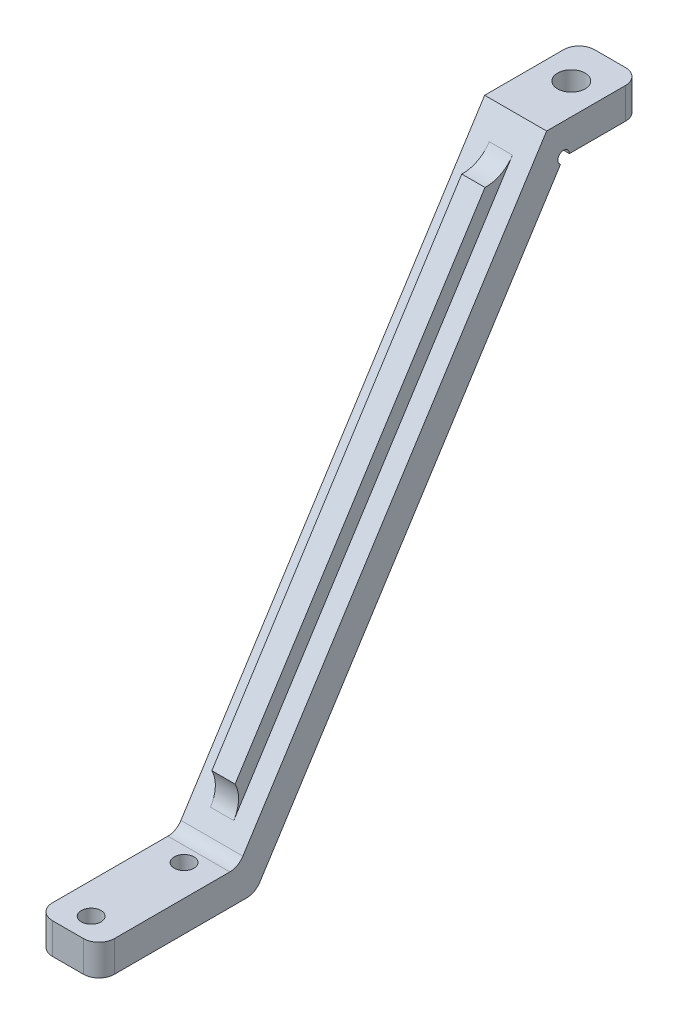
SolidWorks part; units mm, degrees
material "ABS"
ref_plane "前视基准面" through (0, 0, 0) normal (0, 0, 1) x (1, 0, 0)
ref_plane "上视基准面" through (0, 0, 0) normal (0, 1, 0) x (1, 0, 0)
ref_plane "右视基准面" through (0, 0, 0) normal (1, 0, 0) x (0, 0, -1)
other "Configuration Table"
sketch "草图1" plane through (0, 0, 0) normal (1, 0, 0) x (0, 0, -1)
  line L0 (-18, 0) -> (0, 0)
  line L1 (0, 0) -> (39.8071, 62.4)
  line L2 (39.8071, 62.4) -> (52, 62.4)
  line L3 (52, 62.4) -> (52, 58.4)
  line L4 (52, 58.4) -> (42, 58.4)
  line L5 (42, 58.4) -> (2.1929, -4)
  line L6 (2.1929, -4) -> (-18, -4)
  line L7 (-18, -4) -> (-18, 0)
  point P3 (82.8922, 68.3831)
  point P10 (42, 58.4)
  point P12 (51.9561, 62.4)
  dimension "D1" = 4
  dimension "D2" = 4
  dimension "D3" = 4
  dimension "D4" = 18
  dimension "D5" = 10
extrude "凸台-拉伸1" add sketch "草图1" along normal mid plane 8
sketch "草图2" plane through (0, 0, 0) normal (0, 1, 0) x (1, 0, 0)
  line L0 (0, -15) -> (0, -3) construction
  line L1 (0, -9) -> (4, -9) construction
  line L2 (4, 0) -> (4, -18) construction
  circle A0 centre (0, -3) radius 1.275
  circle A1 centre (0, -15) radius 1.275
  dimension "D1" = 2.55
  dimension "D2" = 12
extrude "切除-拉伸1" cut sketch "草图2" against normal through all both and the other way through all
sketch "草图3" plane through (0, 62.4, 0) normal (0, 1, 0) x (1, 0, 0)
  circle A1 centre (0, 47) radius 1.775
  circle A2 centre (0, 47) radius 1.6 construction
  dimension "D1" = 3.55
extrude "切除-拉伸2" cut sketch "草图3" against normal through all both and the other way through all
sketch "草图4" plane through (0, 0, 0) normal (1, 0, 0) x (0, 0, -1)
  line L0 (3.769, 5.9082) -> (2.0829, 6.9838)
  line L1 (39.8071, 62.4) -> (0, 0) construction
  line L2 (2.0829, 6.9838) -> (34.352, 57.5675)
  line L3 (34.352, 57.5675) -> (36.0381, 56.4918)
  line L4 (36.0381, 56.4918) -> (3.769, 5.9082)
  line L5 (19.9036, 31.2) -> (18.2174, 32.2756) construction
  line L6 (39.4103, 54.3406) -> (41.0965, 53.2649)
  line L7 (2.1929, -4) -> (42, 58.4) construction
  line L8 (41.0965, 53.2649) -> (8.8274, 2.6813)
  line L9 (8.8274, 2.6813) -> (7.1413, 3.7569)
  line L10 (7.1413, 3.7569) -> (39.4103, 54.3406)
  dimension "D1" = 2
  dimension "D2" = 60
  dimension "D3" = 2
extrude "凸台-拉伸2" add sketch "草图4" along normal mid plane 3
sketch "草图5" plane through (4, 0, 0) normal (1, 0, 0) x (0, 0, -1)
  circle A0 centre (42, 58.4) radius 0.75
  dimension "D1" = 1.5
extrude "切除-拉伸3" cut sketch "草图5" against normal through all both and the other way through all
fillet "圆角2" radius 4 4 edges at (0, 3.7569, -7.1413) (0, 5.9082, -3.769) (0, 56.4918, -36.0381) (0, 54.3406, -39.4103)
fillet "圆角3" radius 2 4 edges at (-4, -2, 18) (4, -2, 18) (-4, 60.4, -52) (4, 60.4, -52)
fillet "圆角4" radius 2 2 edges at (0, 0, 0) (0, -4, -2.1929)
